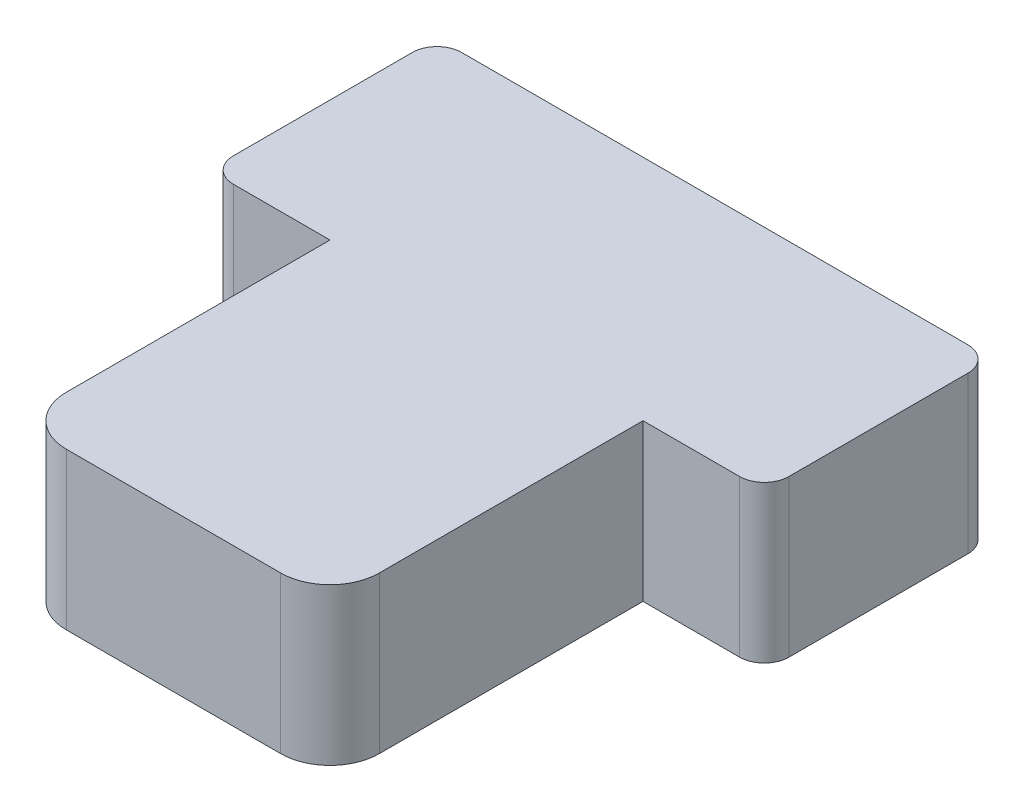
SolidWorks part; units mm, degrees
material "Beech"
ref_plane "Front Plane" through (0, 0, 0) normal (0, 0, 1) x (1, 0, 0)
ref_plane "Top Plane" through (0, 0, 0) normal (0, 1, 0) x (1, 0, 0)
ref_plane "Right Plane" through (0, 0, 0) normal (1, 0, 0) x (0, 0, -1)
sketch "Sketch1" plane through (0, 0, 0) normal (0, 1, 0) x (1, 0, 0)
  line L0 (0, 0) -> (6.35, 0)
  line L1 (0, 0) -> (0, 6.35)
  line L2 (6.35, 0) -> (6.35, 6.35)
  line L4 (-2.46, 10.9807) -> (-2.46, 6.35)
  line L5 (-2.46, 10.9807) -> (8.81, 10.9807)
  line L6 (-2.46, 6.35) -> (0, 6.35)
  line L7 (8.81, 10.9807) -> (8.81, 6.35)
  line L8 (6.35, 6.35) -> (8.81, 6.35)
  dimension "D1" = 6.35
  dimension "D2" = 6.35
  dimension "D3" = 11.27
  dimension "D4" = 4.6307
extrude "MotorSupport_Extrude" add sketch "Sketch1" along normal blind 3.175
fillet "MotorSupport_BottomFillet" radius 1 2 edges at (0, 1.5875, 0) (6.35, 1.5875, 0)
fillet "MotorSupport_TopFillet" radius 0.5 4 edges at (-2.46, 1.5875, -6.35) (-2.46, 1.5875, -10.9807) (8.81, 1.5875, -10.9807) (8.81, 1.5875, -6.35)
equation "\"CageLeftBottomEdge\"=22.11mm"
equation "\"CageLeftTopEdge\"=22.11mm"
equation "\"CageRightBottomEdge\"=21.63mm"
equation "\"CageRightTopEdge\"=21.63mm"
equation "\"CageHeight\"=86.04mm"
equation "\"CageLength\"=73.76mm"
equation "\"CageTopScrewClearance\"=10mm"
equation "\"CageBottomScrewClearance\"=25mm"
equation "\"CageLeftTopDepth\"= 11.65mm"
equation "\"CageLeftBottomDepth\"=11.11mm"
equation "\"CageLeftTopHeight\"=8.56175mm"
equation "\"CageLeftBottomHeight\"=16mm"
equation "\"CageRightTopDepth\"= 11.05mm"
equation "\"CageRightBottomDepth\"=10.58mm"
equation "\"CageRightTopHeight\"=9.6mm"
equation "\"CageRightBottomHeight\"=15.49mm"
equation "\"CageLeftTopChannelDepth\"=2.41908mm"
equation "\"CageLeftBottomChannelDepth\"=2.588mm"
equation "\"CageLeftChannelHeight\"=11.7mm"
equation "\"CageRightTopChannelDepth\"=2.32mm"
equation "\"CageRightBottomChannelDepth\"=2.318mm"
equation "\"CageRightChannelHeight\"=10mm"
equation "\"CageChanRelHeight\"=23.99mm"
equation "\"CageChanRelDepth\"=5.492mm"
equation "\"CageChamberRadius\"=16.261mm"
equation "\"CageScrewDiameter\"=4.8mm"
equation "\"CageSetScrewDiameter\"=3.5mm"
equation "\"CageAxleRadius\"=6.639mm"
equation "\"CageAxleKeyHeight\"=1.619mm"
equation "\"CageAxleKeyWidth\"=2.662mm"
equation "\"CageHoseWindowWidth\"=16.29mm"
equation "\"CageHoseWindowHeight\"=26.5mm"
equation "\"CageHoseWindow-Edge\"=8.89mm"
equation "\"CageScrew-VerticalEdge\"=5.0mm"
equation "\"CageScrew-HorizontalEdge\"=7.5mm"
equation "\"CageScrew-HoseCornerScrewEdge\"=4.45mm"
equation "\"CageAxle-BottomEdge\"=56.05mm"
equation "\"CageAxle-FrontEdge\"=46.03mm"
equation "\"CageBackSetScrew-Axle\"=40mm"
equation "\"CageFrontSetScrew-Axle\"=22mm"
equation "\"CageVelocityWindow-BackEdge\"=34.8mm"
equation "\"CageVelocityWindow-BottomEdge\"=27.55mm"
equation "\"CageVelocityWindowHeight\"=22.29mm"
equation "\"CageVelocityWindowWidth\"=12.61mm"
equation "\"TriggerSlot-BottomEdge\"=6.35mm"
equation "\"TriggerSlot-FrontEdge\"=15mm"
equation "\"TriggerSlotSize\"=6.7mm"
equation "\"TriggerRackOffset\"=.236224in"
equation "\"TriggerSlotSizeInt\"=.25in"
equation "\"MotorMountLegLength\"=.25in"
equation "\"GearOffset\"=.264907in"
equation "\"TriggerSlotSpacing\"=.25in"
equation "\"whitemotordepth\"=11.27mm"
equation "\"whitemotorbackdepth\"=3.845mm"
equation "\"whitemotoraxledepth\" = 3.5mm"
equation "\"whitemotoraxleoffset\"=11.4mm"
equation "\"whitemotorwidth\"=12.07mm"
equation "\"whitemotorheight\"=16.68mm"
equation "\"whitemotorcylinderlength\" =13.04mm"
equation "\"whitemotorcylinderradius\"=3.845mm"
equation "\"whitemotorcylinderoffset\"=2.35mm"
equation "\"whitemotorcutoutlength\"=1.88mm"
equation "\"whitemotorouterrad\"=5mm"
equation "\"whitemotorinnerrad\"=2.95mm"
equation "\"D1@Sketch1\"=\"TriggerSlotSizeInt\""
equation "\"D2@Sketch1\"=\"MotorMountLegLength\""
equation "\"D3@Sketch1\"=\"whitemotordepth\""
equation "\"D4@Sketch1\"=\"GearOffset\"+\"TriggerRackOffset\"-\"whitemotoraxleoffset\"+\"elasticdepth\"+.005in"
equation "\"D1@MotorSupport_Extrude\"=.125in"
equation "\"TriggerMiniSlotWidth\"=3.5mm"
equation "\"TriggerRackWidth\"=6.5mm"
equation "\"elasticracklength\"=2in"
equation "\"elasticrackpegsize\"=.25in"
equation "\"elasticrackpegbuffer\"=.125in"
equation "\"elasticrackpegspacing\"=1.76476378in"
equation "\"elasticbaybuffer\"=.25in"
equation "\"elasticdepth\"=.125in"
equation "\"elasticbaydepth\"=.75in"
equation "\"motormountwidth\"=12mm"
equation "\"motormountcornerfillet\"=3mm"
equation "\"pandiscradius\"=14in"
equation "\"towermaterialwidth\"=.25in"
equation "\"towerslotlength\"=.5in"
equation "\"towermarkerspace\"=5in"
equation "\"towerslothorizoffset\"=1in"
equation "\"towerslothorizspacing\"=2in"
equation "\"towerslotvertoffset\"=3in"
equation "\"towerslotvertspacing\"=1in"
equation "\"towerheight\"=12in"
equation "\"towerupslot\"=1in"
equation "\"toweraxle\"=.5in"
equation "\"stepperouterrad\"=10mm"
equation "\"stepperscrewsize\"=3.45mm"
equation "\"stepperscrewc2c\"=49.5mm"
equation "\"stepperdepthoffset\"=24mm"
equation "\"stepperhorizoffset\"=22.91mm"
equation "\"shaftslotOD\"=18.8mm"
equation "\"shaftslotID\"=13.28mm"
equation "\"shaftkeywidth\"=2.67mm"
equation "\"shaftkeydepth\"=1.8mm"
equation "\"shaftcollartotaldepth\"=12.5mm"
equation "\"shaftsquaredepth\"=6mm"
equation "\"shaftsetscrewsize\"=3.5mm"
equation "\"shaftkeytightdepth\"=1.85mm"
equation "\"shaftslottightID\"=12.78mm"
equation "\"shaftsetscrewoffset\"=9mm"
equation "\"cagecollartotaldepth\"=10mm"
equation "\"cagecollartotalwidth\"=35mm"
equation "\"cagecollarbasedepth\"=4mm"
equation "\"gearhubintdiam\"=30mm"
equation "\"gearhubintwid\"=15mm"
equation "\"towerspeedwidth\"=2in"
equation "\"towerspeedheight\"=8in"
equation "\"towerspeedgap\"=2in"
equation "\"stepperaxleflat\"=.037in"
equation "\"stepperaxlerad\"=0.11811024in"
equation "\"ajaxaxlesize\"=3.87mm"
equation "\"ajaxinnercut\"=2.3mm"
equation "\"ajaxwidth\"=6.1mm"
equation "\"ajaxdiametral\"=25.8854"
equation "\"ajaxcutoutdepth\"=2.3mm"
equation "\"ajax4020gap\"=29.5mm"
equation "\"ajax4010gap\"=24.5mm"
equation "\"ajax20hubbuffer\"=6.1mm"
equation "\"ajax20hubholeoffset\"=.19685in"
equation "\"ajax20hubholesize\"=.059055in"
equation "\"ajax20cutoutint\"=13.4mm"
equation "\"ajax40hubholesize\"=7.21mm"
equation "\"ajax40hubholeoffset\"=10mm"
equation "\"ajax40hubbuffer\"=8.9mm"
equation "\"ajax40cutoutint\"=32.6mm"
equation "\"bearingpandiscrad\"=6.8in"
equation "\"bearingpandiscang\"=48.75deg"
equation "\"bearingclearholedist\"=4.7345in"
equation "\"bearingclearholesize\"=.5in"
equation "\"bearingclearholeang\"=22.5deg"
equation "\"bearingmountholedist\"=4.25in"
equation "\"bearingwirehole\"=1.5in"
equation "\"no6diam\"=.146in"
equation "\"shortconangle\"=20deg"
equation "\"shortconlen\"=.875in"
equation "\"longconlen\"=1.25in"
equation "\"longconangle\"=15deg"
